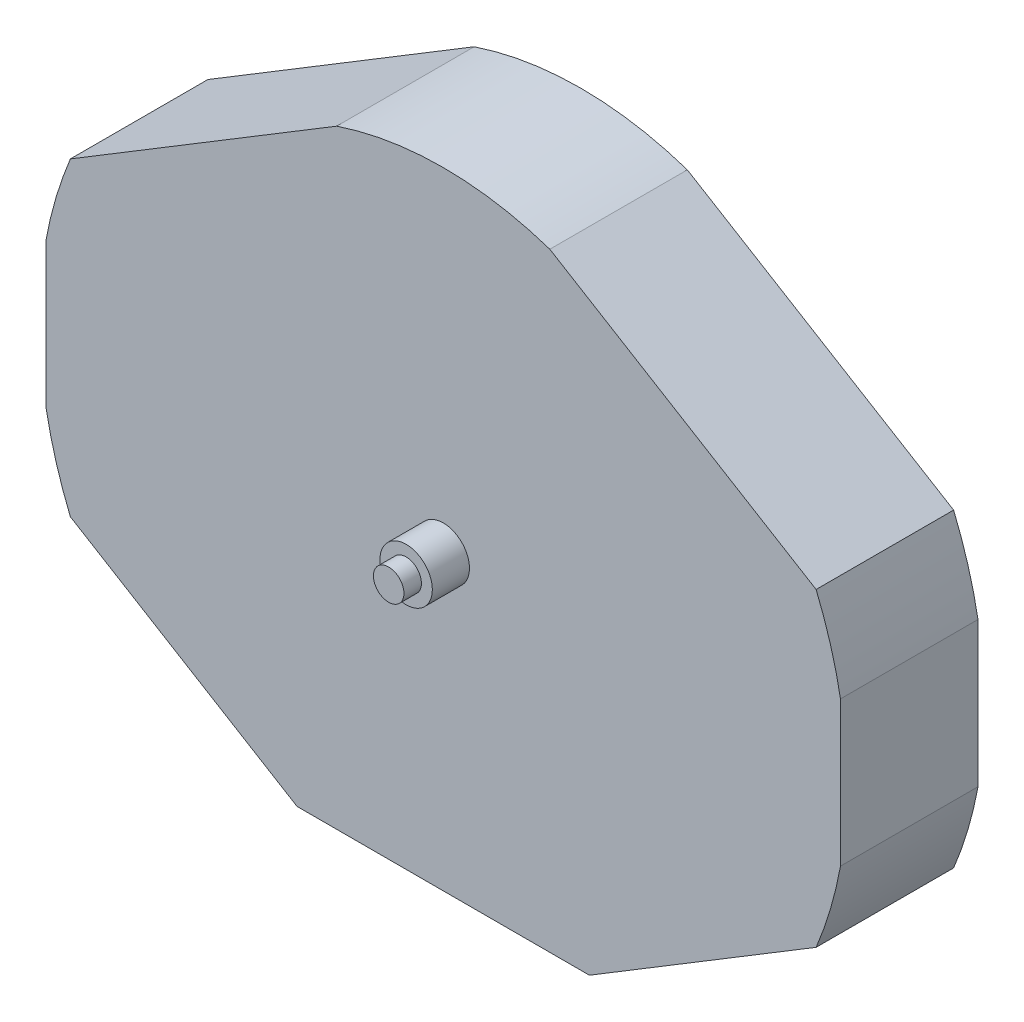
SolidWorks part; units mm, degrees
ref_plane "Plan de face" through (0, 0, 0) normal (0, 0, 1) x (1, 0, 0)
ref_plane "Plan de dessus" through (0, 0, 0) normal (0, 1, 0) x (1, 0, 0)
ref_plane "Plan de droite" through (0, 0, 0) normal (1, 0, 0) x (0, 0, -1)
sketch "Esquisse2" plane through (0, 0, 0) normal (0, 0, 1) x (1, 0, 0)
  line L0 (9.1, 1.6591) -> (9.1, -1.6591)
  line L1 (0, 0) -> (0, 7.65) construction
  line L2 (0, 0) -> (12.4009, 0) construction
  line L3 (2.4413, 7.25) -> (8.5417, 3.55)
  line L4 (-9.1, 1.6591) -> (-9.1, -1.6591)
  line L5 (-2.4413, 7.25) -> (-8.5417, 3.55)
  line L6 (-3.3481, -6.7) -> (3.3481, -6.7)
  line L8 (0, 0) -> (0, -6.7) construction
  line L10 (-3.3481, -6.7) -> (-8.5417, -3.55)
  line L11 (3.3481, -6.7) -> (8.5417, -3.55)
  arc A0 (2.4413, 7.25) -> (-2.4413, 7.25) centre (0, 0) ccw
  arc A1 (9.1, 1.6591) -> (8.5417, 3.55) centre (0, 0) ccw
  arc A2 (-9.1, 1.6591) -> (-8.5417, 3.55) centre (0, 0) cw
  arc A6 (-9.1, -1.6591) -> (-8.5417, -3.55) centre (0, 0) ccw
  arc A7 (9.1, -1.6591) -> (8.5417, -3.55) centre (0, 0) cw
  point P1 (-9.1, 0)
  point P6 (2.4413, 7.25)
  point P8 (8.5417, 3.55)
  point P11 (-2.4413, -7.25)
  point P14 (-8.5417, 3.55)
  point P15 (-2.4413, 7.25)
  point P22 (9.1, 0)
  point P23 (-8.5417, -3.55)
  point P24 (8.5417, -3.55)
  point P25 (2.4413, -7.25)
  dimension "D1" = 15.3
  dimension "D4" = 9.25
  dimension "D2" = 18.2
  dimension "D3" = 7.1
  dimension "D5" = 7.25
  dimension "D6" = 6.7
  dimension "D7" = 31.238
extrude "Boss.-Extru.1" add sketch "Esquisse2" along normal blind 3.15
sketch "Esquisse3" plane through (0, 0, 3.15) normal (0, 0, 1) x (1, 0, 0)
  line L0 (0, 7.65) -> (0, 0) construction
  line L1 (0, 0) -> (9.1, 0) construction
  line L2 (9.1, -1.6591) -> (9.1, 1.6591) construction
  arc A0 (2.4413, 7.25) -> (-2.4413, 7.25) centre (0, 0) ccw construction
  point P0 (-7.9, -3)
  point P1 (8.234, -1.9)
  dimension "D1" = 1.9
  dimension "D2" = 8.234
  dimension "D3" = 3
  dimension "D4" = 7.9
ref_axis "DH1" through (-7.9, -3, 3.15) along (0, 0, 1)
ref_axis "DH2" through (8.234, -1.9, 3.15) along (0, 0, 1)
sketch "Esquisse4" plane through (0, 0, 3.15) normal (0, 0, 1) x (1, 0, 0)
  circle A0 centre (0, 0) radius 0.6
  dimension "D1" = 1.2
extrude "Boss.-Extru.2" add sketch "Esquisse4" along normal blind 0.85
sketch "Esquisse5" plane through (0, 0, 4) normal (0, 0, 1) x (1, 0, 0)
  circle A0 centre (0, 0) radius 0.35
  dimension "D1" = 0.7
extrude "Boss.-Extru.3" add sketch "Esquisse5" along normal blind 0.4
